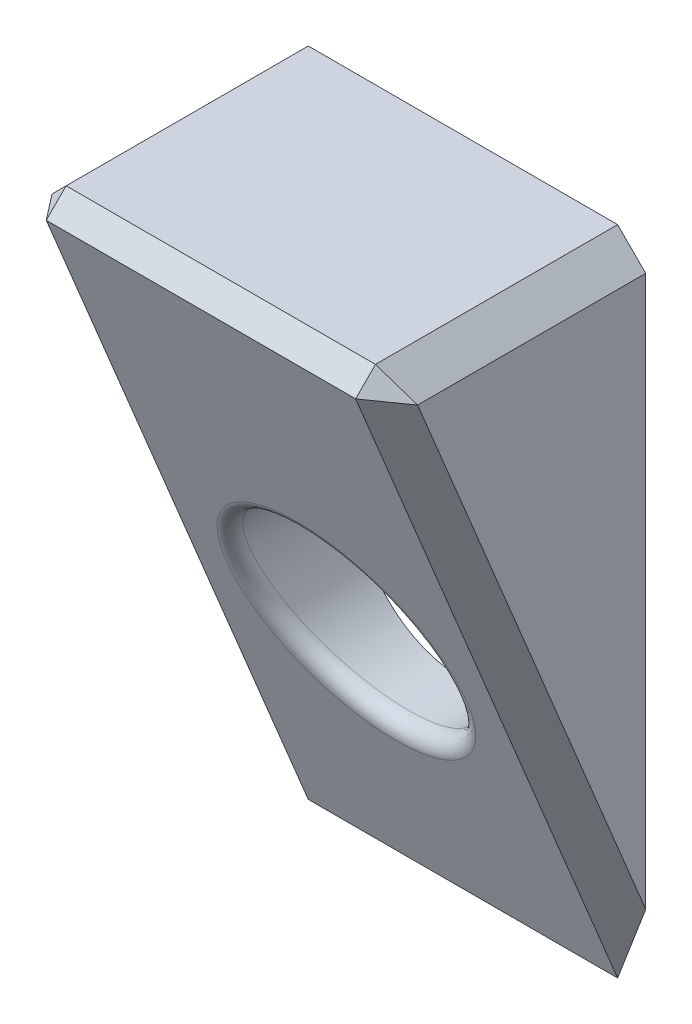
SolidWorks part; units mm, degrees
ref_plane "Plano frontal" through (0, 0, 0) normal (0, 0, 1) x (1, 0, 0)
ref_plane "Plano superior" through (0, 0, 0) normal (0, 1, 0) x (1, 0, 0)
ref_plane "Plano direito" through (0, 0, 0) normal (1, 0, 0) x (0, 0, -1)
sketch "Esboço1" plane through (0, 0, 0) normal (0, 0, 1) x (1, 0, 0)
  line L8 (14, -18.0326) -> (14, 5.1674)
  line L9 (14, 5.1674) -> (1, 5.1674)
  line L10 (1, 5.1674) -> (1, -18.0326)
  line L11 (1, -18.0326) -> (14, -18.0326)
  circle A2 centre (7.5, -7.8326) radius 3.75
  dimension "D1" = 23.2
  dimension "D2" = 13
sketch "Esboço2" plane through (0, 0, 0) normal (1, 0, 0) x (0, 0, -1)
  line L1 (0, 5.1674) -> (0, -18.0326) construction
  line L4 (0, 5.1674) -> (0, -18.0326)
  line L5 (0, 5.1674) -> (-9.6098, 5.1674)
  line L6 (-9.6098, 5.1674) -> (0, -18.0326)
  dimension "D1" = 22.5
extrude "Ressalto-extrusão1" add sketch "Esboço2" along normal blind 13
sketch "Esboço3" plane through (0, 0, 0) normal (0, 0, -1) x (-1, 0, 0)
  line L0 (-13, -7.8326) -> (0, -7.8326) construction
  line L1 (-13, -18.0326) -> (-13, 5.1674) construction
  line L2 (0, -18.0326) -> (0, 5.1674) construction
  circle A1 centre (-6.5, -7.8326) radius 3.75
  point P0 (-3.1256, -7.8326)
  point P1 (-6.5, -7.8326)
  point P9 (-7.5, -7.8326)
extrude "Corte-extrusão1" cut sketch "Esboço3" against normal blind 15
chamfer "Chanfro1" distance 1 angle 45 5 edges at (0, 5.1674, 4.8049) (0, -6.4326, 4.8049) (6.5, 5.1674, 9.6098) (13, 5.1674, 4.8049) (13, -6.4326, 4.8049)
fillet "Filete1" radius 0.5 1 edges at (6.5, -11.5826, 2.6717)
